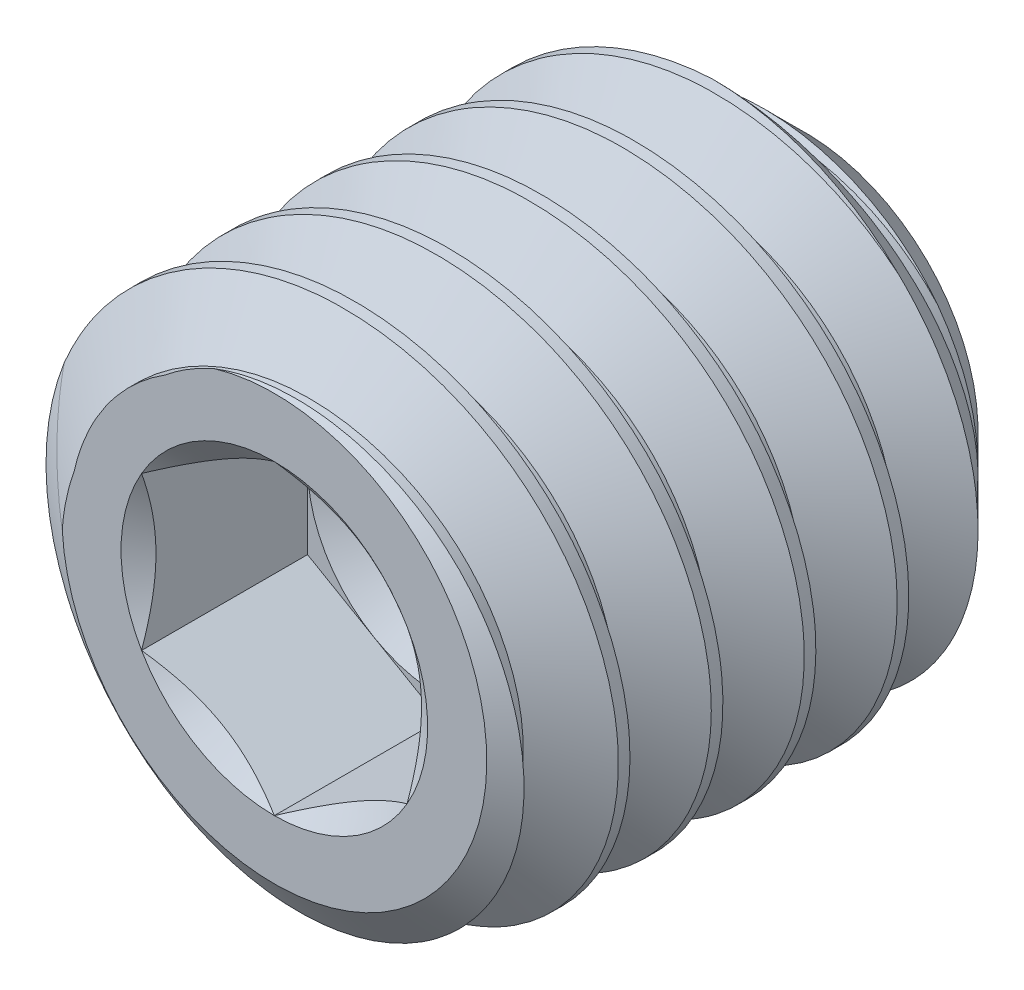
SolidWorks part; units mm, degrees
ref_plane "Front" through (0, 0, 0) normal (0, 0, 1) x (1, 0, 0)
ref_plane "Top" through (0, 0, 0) normal (0, 1, 0) x (1, 0, 0)
ref_plane "Right" through (0, 0, 0) normal (1, 0, 0) x (0, 0, -1)
sketch "Revolve Profile" plane through (0, 0, 0) normal (1, 0, 0) x (0, 0, -1)
  line L0 (-2, 0) -> (-2, 1.6)
  line L1 (-2, 1.6) -> (-1.7199, 2)
  line L2 (-1.7199, 2) -> (1.3, 2)
  line L3 (1.3, 2) -> (2, 1.3)
  line L4 (-0.21, 2) -> (-0.21, -2) construction
  line L5 (2, 0) -> (-2, 0)
  line L6 (-2, 1.6) -> (-2, -1.6) construction
  line L7 (2, 0) -> (2, 1.3)
  point P11 (-0.21, 0)
  dimension "Length" = 4
  dimension "D3" = 35
  dimension "D6" = 45
  dimension "Dia" = 4
  dimension "D1" = 3.2
  dimension "D2" = 0.7
revolve "Body Revolve" add sketch "Revolve Profile" angle 360 about L5
ref_plane "Plane1" through (0, 0, -2) normal (0, 0, 1) x (1, 0, 0)
sketch "Sketch27" plane through (0, 0, -2) normal (0, 0, 1) x (1, 0, 0)
  circle A0 centre (0, 0) radius 2 construction
  circle A1 centre (0, 0) radius 2
curve "Helix/Spiral1" pitch 0.7 height 4.7 radius 2 centre (0, 0, -2) axis (0, 0, 1) start towards (0, 1, 0)
sketch "Sketch28" plane through (0, 0, 0) normal (1, 0, 0) x (0, 0, -1)
  line L0 (2, 2) -> (2.6125, 2)
  line L1 (2.6125, 2) -> (2.35, 1.5453)
  line L2 (2.35, 1.5453) -> (2.2625, 1.5453)
  line L3 (2.2625, 1.5453) -> (2, 2)
  line L4 (2.1313, 1.7727) -> (2.4813, 1.7727) construction
  line L6 (-1.7199, 2) -> (1.3, 2) construction
  dimension "D1" = 0.0875
  dimension "D3" = 60
  dimension "D2" = 0.35
sweep "Cut-Sweep2" cut profiles "Sketch28" path "Helix/Spiral1" align with end faces yes
sketch "Sketch23" plane through (0, 0, 2) normal (0, 0, 1) x (1, 0, 0)
  line L1 (0, 1.1547) -> (-1, 0.5774)
  line L2 (-1, 0.5774) -> (-1, -0.5774)
  line L3 (-1, -0.5774) -> (0, -1.1547)
  line L4 (0, -1.1547) -> (1, -0.5774)
  line L5 (1, -0.5774) -> (1, 0.5774)
  line L6 (1, 0.5774) -> (0, 1.1547)
  circle A0 centre (0, 0) radius 1 construction
  dimension "Hex" = 2
extrude "Cut-Extrude10" cut sketch "Sketch23" against normal blind 1.25
sketch "Sketch24" plane through (0, 0, 2) normal (0, 0, 1) x (1, 0, 0)
  circle A0 centre (0, 0) radius 1.1547
extrude "Cut-Extrude11" cut sketch "Sketch24" against normal through all draft 55
sketch "Sketch26" plane through (0, 0, 0.75) normal (0, 0, 1) x (1, 0, 0)
  circle A0 centre (0, 0) radius 1 construction
  circle A1 centre (0, 0) radius 1
extrude "Cut-Extrude12" cut sketch "Sketch26" against normal through all draft 60
equation "\"D1@Sketch28\" = \"D4@Helix/Spiral1\" * .125"
equation "\"D2@Sketch28\" = \"D4@Helix/Spiral1\" * .5"
equation "\"D3@Helix/Spiral1\" = \"Length@Revolve Profile\" + \"D4@Helix/Spiral1\""
equation "\"hex Depth@Cut-Extrude10\" = \"Hex@Sketch23\" * .625"
equation "\"D1@Revolve Profile\" = \"Dia@Revolve Profile\" * .8"
equation "\"D2@Revolve Profile\" = \"D4@Helix/Spiral1\""
